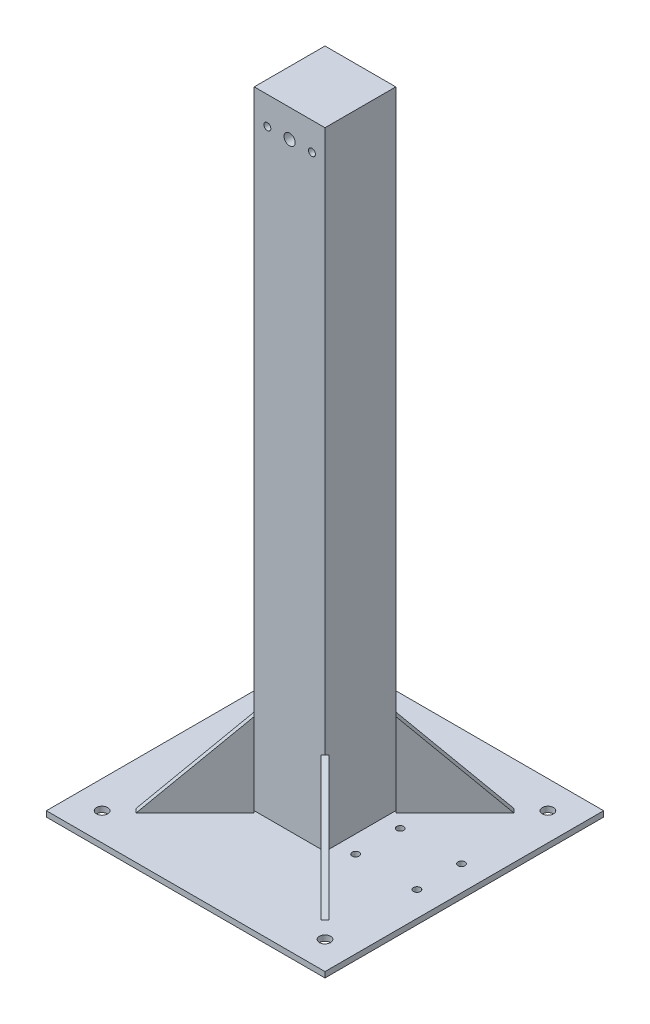
SolidWorks part; units mm, degrees
ref_plane "Plano frontal" through (0, 0, 0) normal (0, 0, 1) x (1, 0, 0)
ref_plane "Plano superior" through (0, 0, 0) normal (0, 1, 0) x (1, 0, 0)
ref_plane "Plano direito" through (0, 0, 0) normal (1, 0, 0) x (0, 0, -1)
sketch "Esboço1" plane through (0, 0, 0) normal (0, 1, 0) x (1, 0, 0)
  line L1 (-100, 100) -> (100, 100)
  line L2 (-100, 100) -> (-100, -100)
  line L3 (-100, -100) -> (100, -100)
  line L4 (100, 100) -> (100, -100)
  line L5 (-100, 100) -> (100, -100) construction
  line L6 (-100, -100) -> (100, 100) construction
  point P0 (0, 0)
  dimension "D1" = 200
  dimension "D2" = 200
extrude "Ressalto-extrusão2" add sketch "Esboço1" against normal blind 4
sketch "Esboço2" plane through (0, 0, 0) normal (0, 1, 0) x (1, 0, 0)
  line L1 (-25.4, 25.4) -> (25.4, 25.4)
  line L2 (-25.4, 25.4) -> (-25.4, -25.4)
  line L3 (-25.4, -25.4) -> (25.4, -25.4)
  line L4 (25.4, 25.4) -> (25.4, -25.4)
  line L5 (-25.4, 25.4) -> (25.4, -25.4) construction
  line L6 (-25.4, -25.4) -> (25.4, 25.4) construction
  line L7 (100, 100) -> (-100, 100) construction
  point P0 (0, 0)
  dimension "D1" = 50.8
  dimension "D2" = 50.8
  dimension "D3" = 100
extrude "Ressalto-extrusão3" add sketch "Esboço2" along normal blind 450
sketch "Esboço3" plane through (0, 0, 0) normal (0, 1, 0) x (1, 0, 0)
  line L0 (-100, -100) -> (100, -100) construction
  line L1 (100, -100) -> (100, 100) construction
  circle A0 centre (80, -80) radius 4
  circle A1 centre (80, 80) radius 4
  circle A2 centre (-80, 80) radius 4
  circle A3 centre (-80, -80) radius 4
  dimension "D1" = 8
  dimension "D3" = 20
  dimension "D2" = 20
extrude "Corte-extrusão1" cut sketch "Esboço3" against normal blind 4
sketch "Esboço5" plane through (0, 0, 0) normal (0, 0, 1) x (1, 0, 0)
  line L0 (25.4, 450) -> (25.4, 0) construction
  line L1 (-25.4, 0) -> (25.4, 0) construction
  circle A0 centre (0, 430) radius 4
  circle A1 centre (16, 430) radius 2.5
  circle A2 centre (-16, 430) radius 2.5
  dimension "D1" = 5
  dimension "D2" = 8
  dimension "D3" = 5
  dimension "D4" = 9.4
  dimension "D5" = 25.4
  dimension "D6" = 32
  dimension "D7" = 430
extrude "Corte-extrusão2" cut sketch "Esboço5" against normal blind 25.4 and the other way blind 25.4
sketch "Esboço6" plane through (0, 0, 0) normal (0, 1, 0) x (1, 0, 0)
  line L0 (100, 100) -> (-100, 100) construction
  line L1 (100, -100) -> (100, 100) construction
  circle A0 centre (82, 16) radius 2.5
  circle A1 centre (82, -16) radius 2.5
  circle A4 centre (38, 16) radius 2.5
  circle A5 centre (38, -16) radius 2.5
  dimension "D1" = 32
  dimension "D5" = 5
  dimension "D2" = 44
  dimension "D3" = 84
  dimension "D4" = 18
extrude "Corte-extrusão3" cut sketch "Esboço6" against normal blind 4
sketch "Esboço7" plane through (0, 0, 0) normal (0, 1, 0) x (1, 0, 0)
  line L0 (100, -100) -> (-100, 100)
  point P2 (0, 0)
  point P3 (0, 0)
ref_plane "Plano1" through (0, 0, 0) normal (0.7071, 0, -0.7071) x (-0.7071, 0, -0.7071)
sketch "Esboço8" plane through (0, 0, 0) normal (0.7071, 0, -0.7071) x (-0.7071, 0, -0.7071)
  line L0 (35.921, 0) -> (95.921, 0)
  line L1 (95.921, 0) -> (35.921, 60)
  line L2 (35.921, 60) -> (35.921, 0)
  line L4 (-35.921, 0) -> (-95.921, 0)
  line L5 (-95.921, 0) -> (-35.921, 60)
  line L6 (-35.921, 60) -> (-35.921, 0)
  point P5 (0, 0)
  point P6 (0, 0)
  point P7 (0, 0)
  point P8 (0, 0)
  point P9 (0, 0)
  point P10 (0, 0)
  point P12 (0, 0)
  point P13 (0, 0)
  point P14 (0, 0)
  point P15 (0, 0)
  point P16 (0, 0)
  dimension "D1" = 60
  dimension "D2" = 60
extrude "Ressalto-extrusão7" add sketch "Esboço8" along normal blind 2 and the other way blind 2 separate body
sketch "Esboço9" plane through (0, 0, 0) normal (0, 1, 0) x (1, 0, 0)
  line L0 (100, 100) -> (-100, -100)
  point P2 (0, 0)
  point P3 (0, 0)
ref_plane "Plano2" through (0, 0, 0) normal (-0.7071, 0, -0.7071) x (-0.7071, 0, 0.7071)
sketch "Esboço10" plane through (0, 0, 0) normal (-0.7071, 0, -0.7071) x (-0.7071, 0, 0.7071)
  line L0 (35.921, 0) -> (95.921, 0)
  line L1 (95.921, 0) -> (35.921, 60)
  line L2 (35.921, 60) -> (35.921, 0)
  line L3 (-35.921, 0) -> (-95.921, 0)
  line L4 (-95.921, 0) -> (-35.921, 60)
  line L5 (-35.921, 60) -> (-35.921, 0)
  point P3 (0, 0)
  point P7 (0, 0)
  point P8 (0, 0)
  point P9 (0, 0)
  point P10 (0, 0)
  point P11 (0, 0)
  point P12 (0, 0)
  point P13 (0, 0)
  point P14 (0, 0)
  point P15 (0, 0)
  point P16 (0, 0)
  point P17 (0, 0)
  point P18 (0, 0)
extrude "Ressalto-extrusão8" add sketch "Esboço10" along normal blind 2 and the other way blind 2 separate body
